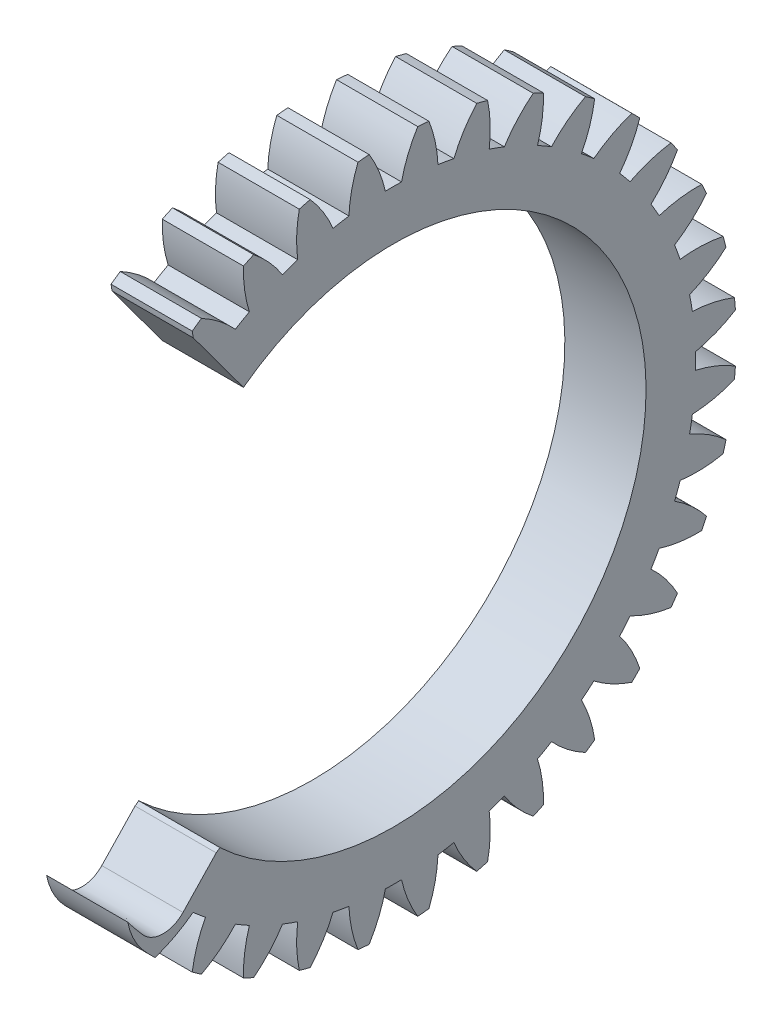
SolidWorks part; units mm, degrees
ref_plane "Plane1" through (0, 0, 0) normal (0, 0, 1) x (1, 0, 0)
ref_plane "Plane2" through (0, 0, 0) normal (0, 1, 0) x (1, 0, 0)
ref_plane "Plane3" through (0, 0, 0) normal (1, 0, 0) x (0, 0, -1)
sketch "HoldingSke" plane through (0, 0, 0) normal (0, 1, 0) x (1, 0, 0)
  line L0 (0, 0) -> (0.4045, -0.2939)
  line L1 (-15, 0) -> (100, 0) construction
  line L2 (0, 0) -> (-2.1039, 2.3779)
  line L3 (0, 0) -> (-11.863, 4.5341)
  line L4 (0, 0) -> (6.9867, 5.0761)
  line L5 (0, 0) -> (-46.8476, -17.4728)
  line L6 (0, 0) -> (-7.4607, -5.0337)
  line L7 (-2.1039, 2.3779) -> (8.6586, 51.2059)
  line L8 (-76.2, 54.61) -> (-71.9, 54.61)
  line L9 (-71.009, 38.7566) -> (-53.1078, 45.2721)
  line L10 (-76.2, 71.12) -> (104.1128, 71.12)
  line L11 (0, 0) -> (-9, 0)
  line L12 (-76.2, 101.6) -> (-76.133, 101.6)
  line L13 (24.9733, 27.94) -> (52.9518, 28.4284)
  line L14 (24.9733, 27.94) -> (24.9743, 27.94)
  line L15 (24.9733, 27.94) -> (100.4006, 29.5858)
  line L16 (-63.627, -2) -> (-12.827, -2)
  circle A0 centre (0, 0) radius 28
  circle A1 centre (0, 0) radius 33.499
  circle A2 centre (0, 0) radius 37.5
  circle A3 centre (0, 0) radius 28
  dimension "Num_teeth" = 36
  dimension "Pitch_radius" = 180.3128
  dimension "Width" = 9
  dimension "Thickness" = 9
sketch "BasProSke" plane through (0, 0, 0) normal (0, 1, 0) x (1, 0, 0)
  line L0 (-10, 0) -> (60, 0) construction
  line L1 (0, 0) -> (0, 38)
  line L2 (0, 0) -> (9, 0)
  line L3 (9, 0) -> (9, 38)
  line L4 (9, 38) -> (0, 38)
  dimension "Thickness" = 9
  dimension "Diameter" = 76
revolve "Base-Revolve" add sketch "BasProSke" angle 360 about L0
sketch "TooCutSke" plane through (0, 0, 0) normal (1, 0, 0) x (0, 0, -1)
  line L1 (0, 0) -> (0, 107) construction
  line L2 (0, 0) -> (-1.6875, 35.9604) construction
  line L3 (0, 0) -> (-6.2701, 71.6676) construction
  line L4 (-1.6875, 35.9604) -> (-3.135, 35.8338) construction
  arc A0 (0.8949, 33.487) -> (-0.8949, 33.487) centre (0, 0) ccw
  arc A1 (2.7061, 37.929) -> (-2.7061, 37.929) centre (0, 0) ccw
  circle A2 centre (0, 0) radius 36 construction
  circle A3 centre (0, 0) radius 33.8289 construction
  arc A4 (-0.8949, 33.487) -> (-2.7061, 37.929) centre (-14.9484, 30.347) ccw
  arc A5 (2.7061, 37.929) -> (0.8949, 33.487) centre (14.9484, 30.347) ccw
extrude "ToothCut" cut sketch "TooCutSke" along normal through all
fillet "Breaks" [suppressed] radius 0.04 tangent propagation no
fillet "RootFillets" [suppressed] radius 0.501
pattern_circular "TeethCuts" count 36 every 10 about axis through (-10, 0, 0) along (1, 0, 0) of "ToothCut", "RootFillets", "Breaks"
sketch "HubNeaOneSke" plane through (0, 0, 0) normal (-1, 0, 0) x (0, 0, 1)
  circle A0 centre (0, 0) radius 33.499
  dimension "Diameter" = 66.998
extrude "HubNearOne" [suppressed] add sketch "HubNeaOneSke" along normal blind 41.0001
sketch "HubNeaBotSke" plane through (0, 0, 0) normal (-1, 0, 0) x (0, 0, 1)
  circle A0 centre (0, 0) radius 33.499
  dimension "Diameter" = 66.998
extrude "HubNearBoth" [suppressed] add sketch "HubNeaBotSke" along normal blind 20.5
ref_plane "FarPln" through (9, 0, 0) normal (1, 0, 0) x (0, 0, -1)
sketch "HubFarSke" plane through (9, 0, 0) normal (1, 0, 0) x (0, 0, -1)
  circle A0 centre (0, 0) radius 33.499
  dimension "Diameter" = 66.998
extrude "HubFar" [suppressed] add sketch "HubFarSke" along normal blind 20.5
sketch "BorSke" plane through (0, 0, 0) normal (1, 0, 0) x (0, 0, -1)
  circle A0 centre (0, 0) radius 28
  dimension "Diameter" = 56
extrude "Bore" cut sketch "BorSke" along normal mid plane 100.0001
sketch "KeySke" plane through (0, 0, 0) normal (1, 0, 0) x (0, 0, -1)
  line L0 (-8, 0) -> (-8, 32.3)
  line L1 (-8, 32.3) -> (8, 32.3)
  line L2 (8, 32.3) -> (8, 0)
  line L3 (0, 0) -> (0, 34) construction
  line L4 (-8, 0) -> (8, 0)
  dimension "Width" = 16
extrude "Keyway" [suppressed] cut sketch "KeySke" along normal mid plane 100.0001
pattern_circular "Keyway2" [suppressed] count 2 every 90 about axis through (-10, 0, 0) along (1, 0, 0) reverse direction yes
sketch "Szkic1" plane through (0, 0, 0) normal (1, 0, 0) x (0, 0, -1)
  line L0 (0, 0) -> (-27.328, 37.0259)
  line L1 (-27.328, 37.0259) -> (-47.6164, -10.233)
  line L2 (-47.6164, -10.233) -> (0, 0)
extrude "Wytnij-wyciągnięcie1" cut sketch "Szkic1" along normal through all
sketch "Szkic2" plane through (0, 0, 0) normal (1, 0, 0) x (0, 0, -1)
  line L0 (-19.6433, -20.6493) -> (-23.3286, -24.5233) construction
  line L1 (-19.6433, -20.6493) -> (-23.3286, -24.5233)
  line L2 (-24.5118, 27.7159) -> (-14.2182, -16.6493)
  line L3 (-14.2182, -16.6493) -> (-19.6433, -20.6493)
  line L4 (-24.5118, 27.7159) -> (-50.9594, 25.255)
  line L5 (-50.9594, 25.255) -> (-37.7356, -29.3697)
  line L6 (-37.7356, -29.3697) -> (-27.7664, -24.4546)
  line L7 (-26.426, -27.3069) -> (-27.3069, -26.426)
  line L8 (-26.426, -27.3069) -> (-25.0675, -25.4318)
  arc A0 (-24.5118, 27.7159) -> (-27.7664, -24.4546) centre (0, 0) ccw construction
  arc A1 (-24.5118, 27.7159) -> (-27.7664, -24.4546) centre (0, 0) ccw
  arc A2 (-27.3069, -26.426) -> (-29.4473, -22.4022) centre (-21.7924, -20.9115) cw
  spline S0 degree 3 poles (90134.8941, 112009.9109) (3463.5772, 4636.7166) (-114.0977, 39.6847) (-27.1426, -24.9996) (-26.9606, -25.1074) (-26.5829, -25.2806) (-26.3868, -25.3469) (-25.9801, -25.4387) (-25.7711, -25.4633) (-25.3572, -25.469) (-25.1483, -25.4503) (-24.7384, -25.37) (-24.5404, -25.3094) (-24.158, -25.1482) (-23.9725, -25.0463) (71.8369, 41.2251) (-3850.0702, 5358.0733) (-87153.6255, 114422.039) knots -65.156449 -65.156449 -65.156449 -65.156449 0.125 0.125 0.25 0.25 0.375 0.375 0.5 0.5 0.625 0.625 0.75 0.75 0.875 0.875 70.913052 70.913052 70.913052 70.913052 only from (-27.7664, -24.4546) to (-23.3286, -24.5233) construction
  spline S1 degree 3 poles (-27.7664, -24.4546) (-27.6277, -24.6121) (-27.4749, -24.7523) (-27.1426, -24.9996) (-26.9606, -25.1074) (-26.5829, -25.2806) (-26.3868, -25.3469) (-25.9801, -25.4387) (-25.7711, -25.4633) (-25.3572, -25.469) (-25.1483, -25.4503) (-24.7384, -25.37) (-24.5404, -25.3094) (-24.158, -25.1482) (-23.9725, -25.0463) (-23.6312, -24.8102) (-23.4733, -24.6754) (-23.3286, -24.5233) knots 0 0 0 0 0.125 0.125 0.25 0.25 0.375 0.375 0.5 0.5 0.625 0.625 0.75 0.75 0.875 0.875 1 1 1 1
extrude "Wytnij-wyciągnięcie2" cut sketch "Szkic2" against normal blind 43 and the other way through all contours A1 L4 L5 L6 | A1 S1 L1 L3 L2 region at (0, -1.5762, 26.5296) region at (0, 4.8425, 39.1923)
extrude "Dodanie-wyciągnięcie1" add sketch "Szkic2<3>" along normal up to surface (9 mm away) contours A2 L6 A1 | S1 L6 A2 L7 L8 region at (0, -25.7946, 26.8655) region at (0, -23.8723, 28.649) up to face at (9, -1.2954, -9.9994)
sketch "Szkic2<3>" plane through (0, 0, 0) normal (1, 0, 0) x (0, 0, -1) same geometry as "Szkic2"
equation "' \"Module@HoldingSke\" = 6.35"
equation "' \"Num_teeth@HoldingSke\" = 12"
equation "' \"Ap@HoldingSke\" =  20"
equation "' \"Ap@HoldingSke\" = 20"
equation "' \"Width@HoldingSke\" = 0.5 * 25.4"
equation "' \"Hub_dia@HoldingSke\"= 1 * 25.4"
equation "' \"Hub_dia@HoldingSke\" = 1 * 25.4"
equation "' \"Overall_len@HoldingSke\" = 1.0 * 25.4"
equation "' \"Bore@HoldingSke\" = 0.75 * 25.4"
equation "' \"T_dim@HoldingSke\" = 0.1 * 25.4"
equation "' \"Width@KeySke\" = 0.25 * 25.4"
equation "' \"Show_teeth@HoldingSke\" = 13"
equation "' \"Backlash@HoldingSke\" = 0.009 * 25.4"
equation "' \"Addendum_fac@HoldingSke\" = 1.0"
equation "' \"Dedendum_fac@HoldingSke\" = 1.25"
equation "' \"Dedendum_add@HoldingSke\" = 0.00005 * 25.4"
equation "' \"Clearance_fac@HoldingSke\" = 0.25"
equation "\"Pitch@HoldingSke\" = 1 / \"Module@HoldingSke\""
equation "\"Overcut_dia@TooCutSke\" = (\"Num_teeth@HoldingSke\" + 2 * \"Addendum_fac@HoldingSke\") / \"Pitch@HoldingSke\" + 0.002 * 25.4"
equation "\"Pitch_dia@TooCutSke\" = \"Num_teeth@HoldingSke\" / \"Pitch@HoldingSke\""
equation "\"Base_dia@TooCutSke\" = \"Num_teeth@HoldingSke\" / \"Pitch@HoldingSke\" * cos((\"Ap@HoldingSke\"  * 3.14159265 / 180))"
equation "\"Root_dia@TooCutSke\" = (\"Num_teeth@HoldingSke\" + 2) / \"Pitch@HoldingSke\" - 2 * (\"Addendum_fac@HoldingSke\" + \"Dedendum_fac@HoldingSke\") / \"Pitch@HoldingSke\" - \"Dedendum_add@HoldingSke\" * 2"
equation "\"Half_ang@TooCutSke\" = 180 / \"Num_teeth@HoldingSke\""
equation "\"Half_CT@TooCutSke\" = \"Num_teeth@HoldingSke\" / \"Pitch@HoldingSke\" * sin((3.14159265 / 2 / \"Num_teeth@HoldingSke\")) / 2 - 7 * \"Backlash@HoldingSke\" / 4"
equation "\"Flank_rad@TooCutSke\" = \"Num_teeth@HoldingSke\" / \"Pitch@HoldingSke\" / 5"
equation "\"Radius@RootFillets\" = \"Clearance_fac@HoldingSke\" / \"Pitch@HoldingSke\" + \"Dedendum_add@HoldingSke\""
equation "\"Break_rad@Breaks\" = 0.02 / \"Pitch@HoldingSke\""
equation "\"Thickness@HoldingSke\" = \"Width@HoldingSke\""
equation "\"OAL@HoldingSke\" = \"Thickness@HoldingSke\""
equation "\"MHD@HoldingSke\" = (\"Num_teeth@HoldingSke\" + 2) / \"Pitch@HoldingSke\" - 2 * (\"Addendum_fac@HoldingSke\" + \"Dedendum_fac@HoldingSke\")  / \"Pitch@HoldingSke\" - \"Dedendum_add@HoldingSke\" * 2"
equation "\"MBD@HoldingSke\" = (\"Num_teeth@HoldingSke\" + 2) / \"Pitch@HoldingSke\" - 2 * (\"Addendum_fac@HoldingSke\" + \"Dedendum_fac@HoldingSke\")  / \"Pitch@HoldingSke\" - \"Dedendum_add@HoldingSke\" * 2 - 0.002 * 25.4"
equation "\"MHD@HoldingSke\" = ((sgn( \"MHD@HoldingSke\" - \"Hub_dia@HoldingSke\" )-1)*( \"MHD@HoldingSke\" - \"Hub_dia@HoldingSke\" ))/-2+ \"Hub_dia@HoldingSke\""
equation "\"MBD@HoldingSke\" = ((sgn( \"MBD@HoldingSke\" - \"Bore@HoldingSke\" )-1)*( \"MBD@HoldingSke\" - \"Bore@HoldingSke\" ))/-2+ \"Bore@HoldingSke\""
equation "\"OAL@HoldingSke\" = ((sgn( \"OAL@HoldingSke\" - \"Overall_len@HoldingSke\" )+1)*( \"OAL@HoldingSke\" - \"Overall_len@HoldingSke\" ))/2 + \"Overall_len@HoldingSke\" + 0.000002 * 25.4"
equation "\"Num_teeth@TeethCuts\" = int( \"Show_teeth@HoldingSke\" ) + 1"
equation "\"Num_teeth@TeethCuts\" = ((sgn( \"Num_teeth@TeethCuts\" - \"Num_teeth@HoldingSke\" )-1)*( \"Num_teeth@TeethCuts\" - \"Num_teeth@HoldingSke\" ))/-2+ \"Num_teeth@HoldingSke\""
equation "\"Num_teeth@TeethCuts\" = ((sgn( \"Num_teeth@TeethCuts\" - 2.0)+1)*( \"Num_teeth@TeethCuts\" - 2.0))/2 +2.0"
equation "\"Angle@TeethCuts\" = 360.0 / \"Num_teeth@HoldingSke\""
equation "\"Diameter@BasProSke\" = (\"Num_teeth@HoldingSke\" + 2 * \"Addendum_fac@HoldingSke\") / \"Pitch@HoldingSke\""
equation "\"Thickness@BasProSke\"  = \"Thickness@HoldingSke\""
equation "' \"Fillet_rad@BasProSke\" =  \"Thickness@HoldingSke\" * 0.05"
equation "' \"Fillet_rad@BasProSke\" = \"Thickness@HoldingSke\" * 0.05"
equation "\"MHD@HoldingSke\" = ((sgn( \"MHD@HoldingSke\" - \"Root_dia@TooCutSke\" )-1)*( \"MHD@HoldingSke\" - \"Root_dia@TooCutSke\" ))/-2+ \"Root_dia@TooCutSke\""
equation "\"Diameter@HubNeaOneSke\" = \"MHD@HoldingSke\""
equation "\"Length@HubNearOne\" = \"OAL@HoldingSke\" - \"Thickness@BasProSke\""
equation "\"Diameter@HubNeaBotSke\" = \"MHD@HoldingSke\""
equation "\"Length@HubNearBoth\" = ( \"OAL@HoldingSke\" - \"Thickness@BasProSke\" ) / 2.0"
equation "\"Thickness@FarPln\" = \"Thickness@BasProSke\""
equation "\"Diameter@HubFarSke\" = \"MHD@HoldingSke\""
equation "\"Length@HubFar\" = ( \"OAL@HoldingSke\" - \"Thickness@BasProSke\" ) / 2.0"
equation "\"Diameter@BorSke\" = \"MBD@HoldingSke\""
equation "\"D1@Bore\" = \"OAL@HoldingSke\" * 2.0"
equation "\"D1@Keyway\" = \"OAL@HoldingSke\" * 2.0"
equation "\"Offset@KeySke\" = \"T_dim@HoldingSke\" + \"MBD@HoldingSke\" / 2.0"
